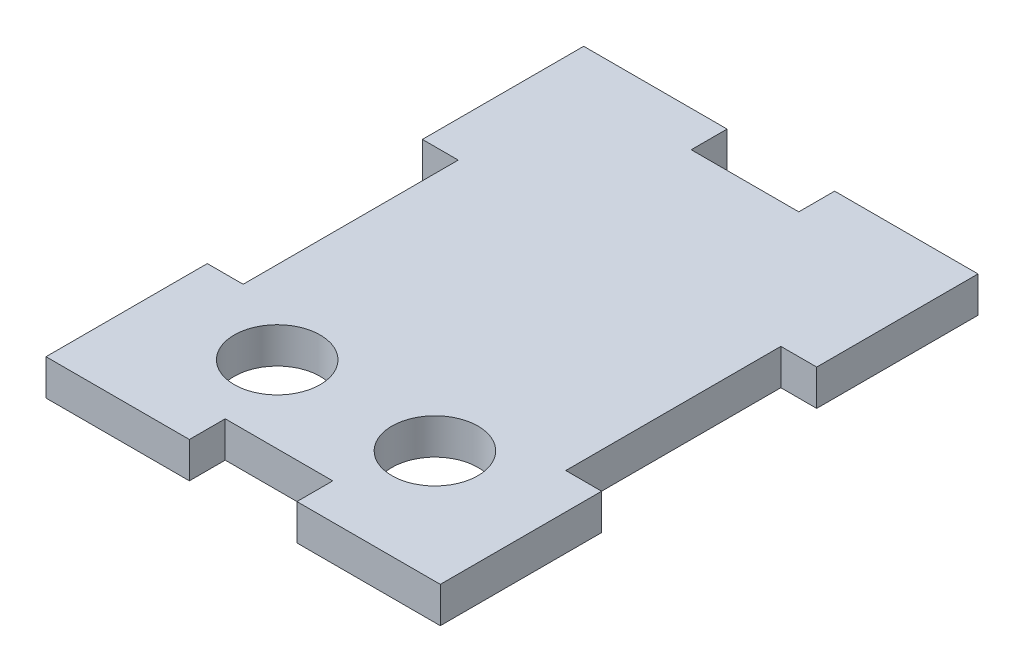
SolidWorks part; units mm, degrees
material "Acrylic (Medium-high impact)"
ref_plane "Front Plane" through (0, 0, 0) normal (0, 0, 1) x (1, 0, 0)
ref_plane "Top Plane" through (0, 0, 0) normal (0, 1, 0) x (1, 0, 0)
ref_plane "Right Plane" through (0, 0, 0) normal (1, 0, 0) x (0, 0, -1)
sketch "Sketch1" plane through (0, 0, 0) normal (0, 1, 0) x (1, 0, 0)
  line L1 (0, 0) -> (55, 0)
  line L2 (0, 0) -> (0, 75)
  line L3 (0, 75) -> (55, 75)
  line L4 (55, 0) -> (55, 75)
  dimension "D1" = 75
  dimension "D2" = 55
extrude "Boss-Extrude1" add sketch "Sketch1" along normal blind 5
sketch "Sketch5" plane through (0, 5, 0) normal (0, 1, 0) x (1, 0, 0)
  line L0 (0, 75) -> (0, 0) construction
  line L1 (0, 22.5) -> (5, 22.5)
  line L2 (0, 22.5) -> (0, 52.5)
  line L3 (0, 52.5) -> (5, 52.5)
  line L4 (5, 22.5) -> (5, 52.5)
  line L5 (55, 75) -> (0, 75) construction
  line L6 (35, 75) -> (20, 75)
  line L7 (35, 75) -> (35, 70)
  line L8 (35, 70) -> (20, 70)
  line L9 (20, 75) -> (20, 70)
  line L10 (55, 0) -> (55, 75) construction
  line L11 (55, 52.5) -> (50, 52.5)
  line L12 (55, 52.5) -> (55, 22.5)
  line L13 (55, 22.5) -> (50, 22.5)
  line L14 (50, 52.5) -> (50, 22.5)
  line L15 (0, 0) -> (55, 0) construction
  line L16 (20, 0) -> (35, 0)
  line L17 (20, 0) -> (20, 5)
  line L18 (20, 5) -> (35, 5)
  line L19 (35, 0) -> (35, 5)
  point P25 (0, 37.5)
  point P26 (27.5, 0)
  dimension "D1" = 5
  dimension "D2" = 30
  dimension "D3" = 15
extrude "Cut-Extrude3" cut sketch "Sketch5" against normal through all both and the other way through all
sketch "Sketch6" plane through (0, 0, 0) normal (0, -1, 0) x (1, 0, 0)
  line L0 (27.5, -5) -> (27.5, -70) construction
  line L1 (5.75, -70) -> (49.25, -70)
  line L2 (5.75, -70) -> (5.75, -26.5)
  line L3 (5.75, -26.5) -> (49.25, -26.5)
  line L4 (49.25, -70) -> (49.25, -26.5)
  line L5 (5.75, -70) -> (49.25, -26.5) construction
  line L6 (5.75, -26.5) -> (49.25, -70) construction
  line L8 (20, -70) -> (35, -70) construction
  point P0 (27.5, -48.25)
  point P5 (0, 0)
  point P6 (27.5, -37.5)
  point P7 (0, 0)
  dimension "D1" = 43.5
extrude "Cut-Extrude4" cut sketch "Sketch6" against normal blind 2.5
sketch "Sketch7" plane through (0, 5, 0) normal (0, 1, 0) x (1, 0, 0)
  line L0 (27.5, 5) -> (27.5, 26.5) construction
  line L2 (49.25, 26.5) -> (5.75, 26.5) construction
  line L3 (20, 5) -> (35, 5) construction
  line L4 (16.5, 15.75) -> (38.5, 15.75) construction
  circle A0 centre (16.5, 15.75) radius 6
  circle A1 centre (38.5, 15.75) radius 6
  point P4 (27.5, 15.75)
  dimension "D1" = 12
  dimension "D2" = 22
extrude "Cut-Extrude5" cut sketch "Sketch7" against normal through all
